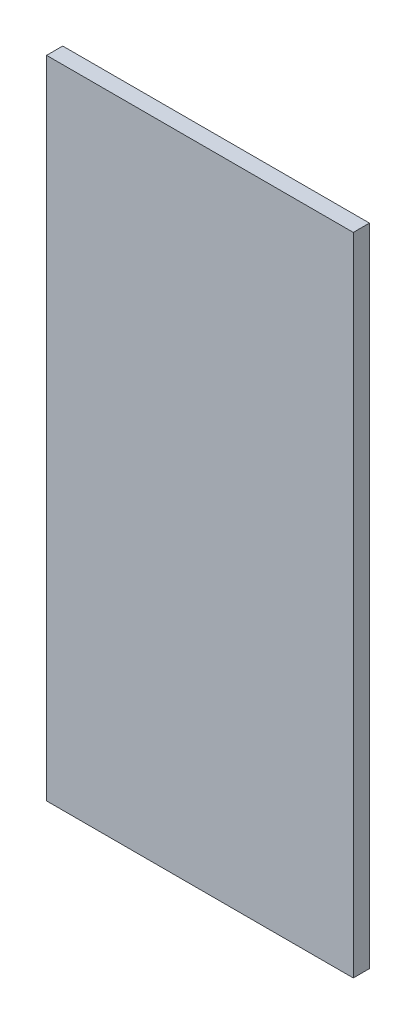
SolidWorks part; units mm, degrees
ref_plane "Спереди" through (0, 0, 0) normal (0, 0, 1) x (1, 0, 0)
ref_plane "Сверху" through (0, 0, 0) normal (0, 1, 0) x (1, 0, 0)
ref_plane "Справа" through (0, 0, 0) normal (1, 0, 0) x (0, 0, -1)
sketch "Эскиз1" plane through (0, 0, 0) normal (0, 0, 1) x (1, 0, 0)
  line L1 (0, 0) -> (19, 0)
  line L2 (0, 0) -> (0, 40)
  line L3 (0, 40) -> (19, 40)
  line L4 (19, 0) -> (19, 40)
  dimension "D1" = 19
  dimension "D2" = 40
extrude "Бобышка-Вытянуть1" add sketch "Эскиз1" along normal blind 1
